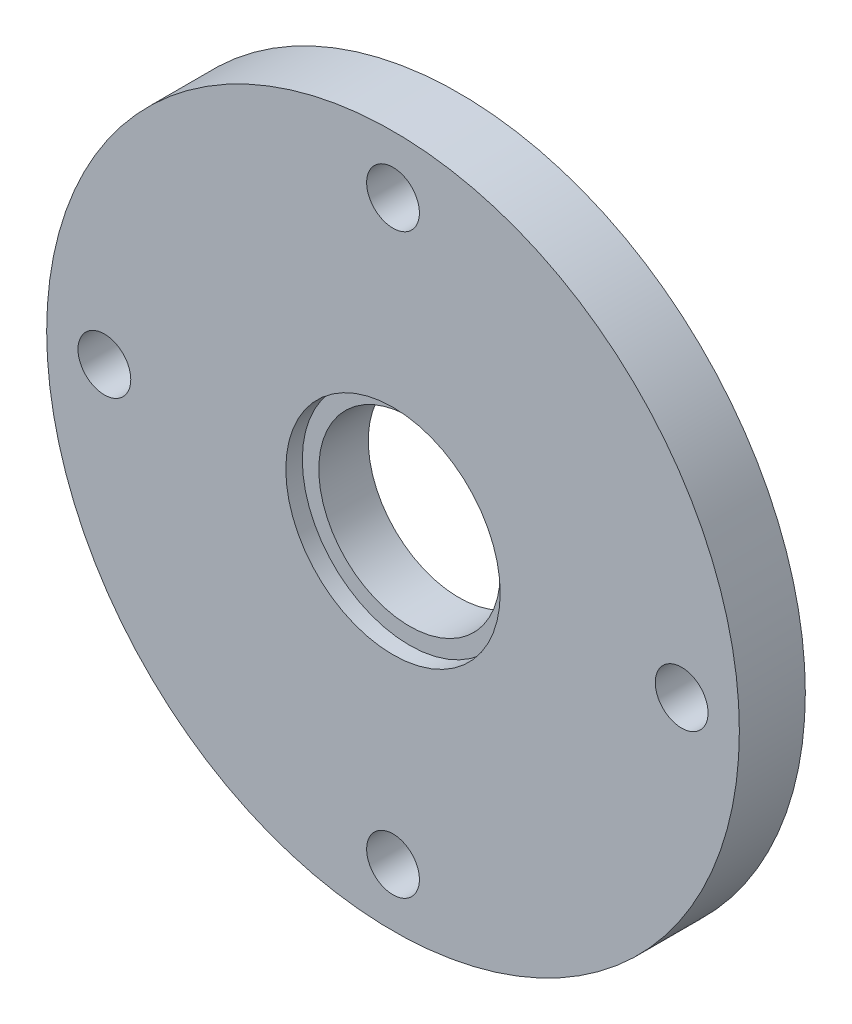
SolidWorks part; units mm, degrees
ref_plane "Front" through (0, 0, 0) normal (0, 0, 1) x (1, 0, 0)
ref_plane "Top" through (0, 0, 0) normal (0, 1, 0) x (1, 0, 0)
ref_plane "Right" through (0, 0, 0) normal (1, 0, 0) x (0, 0, -1)
sketch "Sketch1" plane through (0, 0, 0) normal (0, 0, 1) x (1, 0, 0)
  line L0 (0, 17.5) -> (0, 0) construction
  circle A0 centre (0, 0) radius 21
  circle A1 centre (0, 17.5) radius 1.6
  circle A2 centre (17.5, 0) radius 1.6
  circle A3 centre (0, -17.5) radius 1.6
  circle A4 centre (-17.5, 0) radius 1.6
  circle A5 centre (0, 0) radius 5.5
  point P14 (0, 0)
  dimension "D1" = 3.2
  dimension "D3" = 42
  dimension "D5" = 11
  dimension "D2" = 17.5
  dimension "D4" = 4
extrude "Boss-Extrude1" add sketch "Sketch1" along normal blind 4
sketch "Sketch2" plane through (0, 0, 4) normal (0, 0, 1) x (1, 0, 0)
  circle A0 centre (0, 0) radius 6.5
  dimension "D1" = 13
extrude "Cut-Extrude1" cut sketch "Sketch2" against normal blind 1
hole_wizard "CSK for M3 Flat Head Machine Screw1" positions "Sketch3" profile "Sketch5" countersink size "M3" standard "ANSI Metric" end condition through all
sketch "Sketch3" plane through (0, 0, 0) normal (0, 0, -1) x (-1, 0, 0)
  point P0 (17.5, 0)
  point P3 (0, 17.5)
  point P6 (-17.5, 0)
  point P9 (0, -17.5)
sketch "Sketch5" plane through (-17.5, 0, 0) normal (1, 0, 0) x (0, 1, 0)
  line L0 (0, 0) -> (0, 4)
  line L1 (0, 4) -> (1.6, 4)
  line L2 (1.6, 4) -> (1.6, 1.55)
  line L3 (1.6, 1.55) -> (3.15, 0)
  line L5 (3.15, 0) -> (0, 0)
  line L6 (-1.6, 1.55) -> (-3.15, 0) construction
  line L11 (0, -6.35) -> (0, 107.95) construction
  dimension "Thru Hole Dia." = 3.2
  dimension "Thru Hole Depth" = 4
  dimension "Near C'Sink Dia." = 6.3
  dimension "Near C'Sink Angle" = 90
